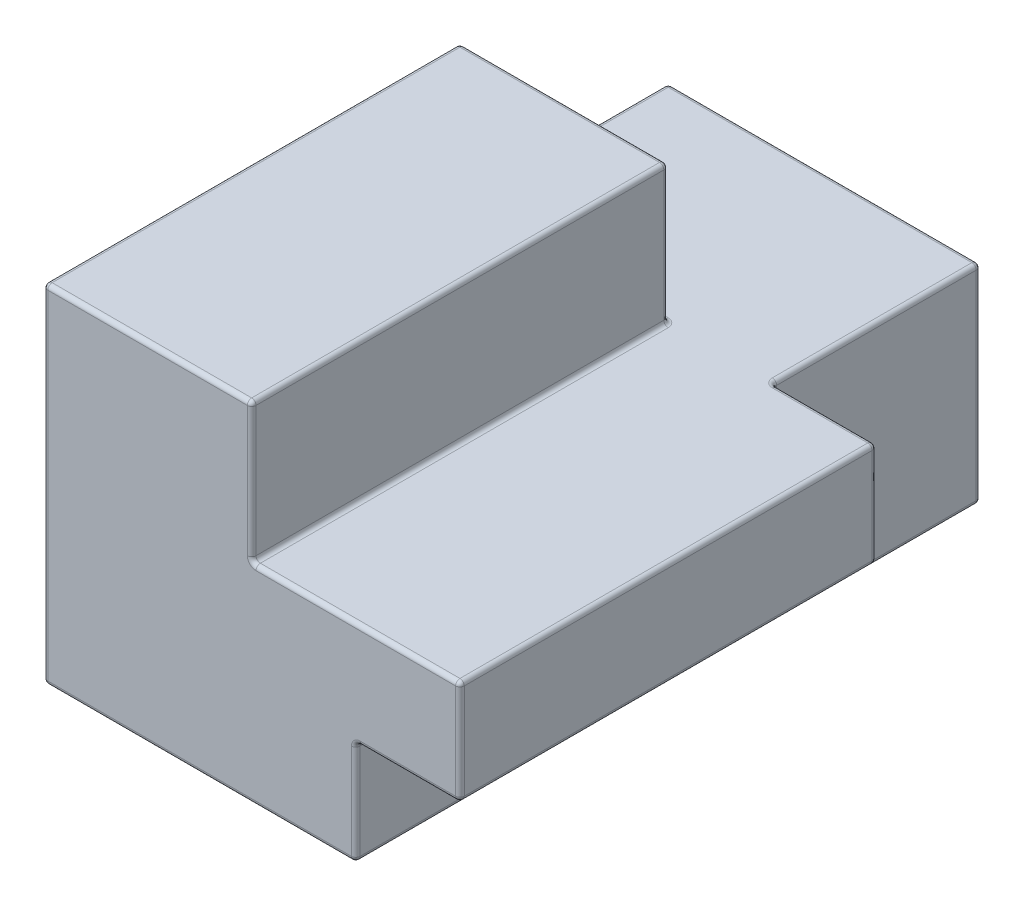
SolidWorks part; units mm, degrees
ref_plane "Front Plane" through (0, 0, 0) normal (0, 0, 1) x (1, 0, 0)
ref_plane "Top Plane" through (0, 0, 0) normal (0, 1, 0) x (1, 0, 0)
ref_plane "Right Plane" through (0, 0, 0) normal (1, 0, 0) x (0, 0, -1)
sketch "Sketch1" plane through (0, 0, 0) normal (1, 0, 0) x (0, 0, -1)
  line L1 (-36, -12) -> (36, -12)
  line L2 (-36, -12) -> (-36, 12)
  line L3 (-36, 12) -> (36, 12)
  line L4 (36, -12) -> (36, 12)
  line L5 (-36, -12) -> (36, 12) construction
  line L6 (-36, 12) -> (36, -12) construction
  line L7 (-36, 12) -> (12, 12)
  line L8 (-36, 12) -> (-36, 28)
  line L9 (-36, 28) -> (12, 28)
  line L10 (12, 12) -> (12, 28)
  line L11 (12, 12) -> (-36, 12)
  line L12 (12, 12) -> (12, 0)
  line L13 (12, 0) -> (-36, 0)
  line L14 (-36, 12) -> (-36, 0)
  point P0 (0, 0)
  dimension "D1" = 72
  dimension "D2" = 12
  dimension "D3" = 24
  dimension "D4" = 24
  dimension "D5" = 40
extrude "Boss-Extrude1" add sketch "Sketch1" along normal blind 36 contours L12 L13 L2 L1 L4 L3 region at (0, -3, -6)
extrude "Boss-Extrude2" add sketch "Sketch1<3>" along normal blind 48 contours L13 L12 L3 L2 region at (0, 6, 12)
sketch "Sketch1<3>" plane through (0, 0, 0) normal (1, 0, 0) x (0, 0, -1) same geometry as "Sketch1"
extrude "Boss-Extrude3" add sketch "Sketch1<4>" along normal blind 24 contours L3 L10 L9 L8 region at (0, 20, 12)
sketch "Sketch1<4>" plane through (0, 0, 0) normal (1, 0, 0) x (0, 0, -1) same geometry as "Sketch1"
fillet "Fillet1" radius 0.5 30 edges at (18, -12, 36) (18, -12, -36) (18, 12, -36) (36, 12, -24) (36, 0, -36) (36, -12, 0) (36, -6, 36) (36, 0, 12) (36, 6, -12) (0, 12, -24) (0, 0, -36) (0, -12, 0) (0, 8, 36) (42, 0, -12) (42, 12, -12) (36, 12, 36) (42, 0, 36) (48, 6, 36) (48, 12, 12) (48, 6, -12) (48, 0, 12) (12, 12, -12) (12, 28, -12) (12, 28, 36) (24, 20, 36) (24, 28, 12) (24, 20, -12) (24, 12, 12) (0, 28, 12) (0, 20, -12)
